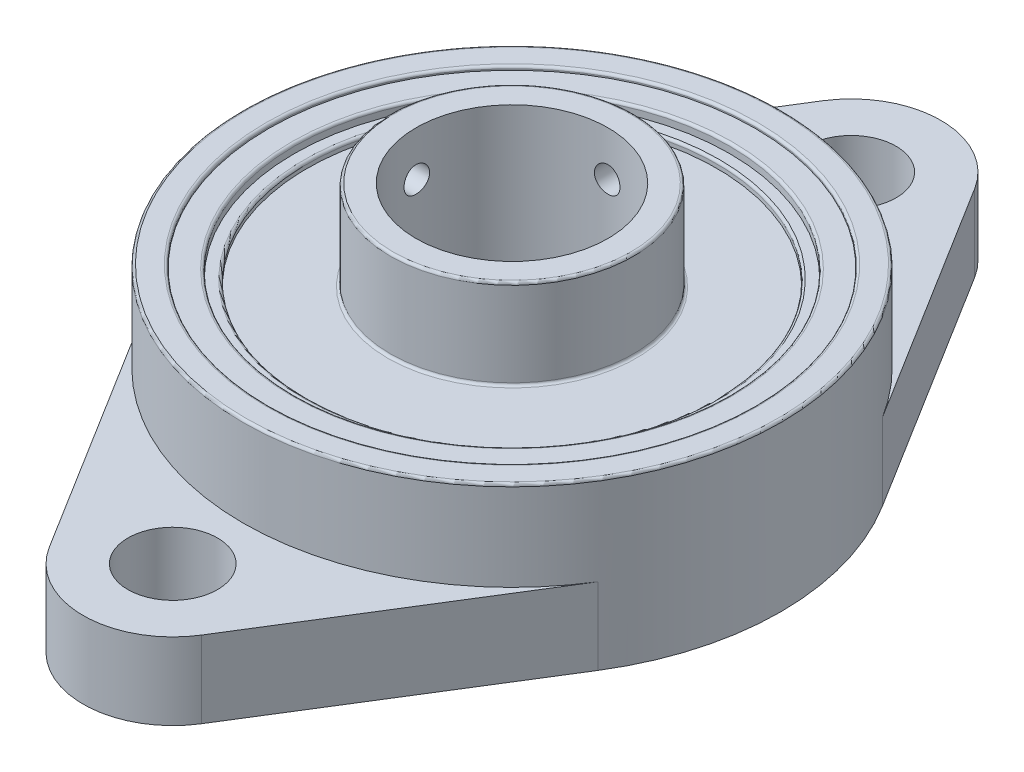
SolidWorks part; units mm, degrees
ref_plane "Front Plane" through (0, 0, 0) normal (0, 0, 1) x (1, 0, 0)
ref_plane "Top Plane" through (0, 0, 0) normal (0, 1, 0) x (1, 0, 0)
ref_plane "Right Plane" through (0, 0, 0) normal (1, 0, 0) x (0, 0, -1)
sketch "Sketch1" plane through (0, 0, 0) normal (0, 1, 0) x (1, 0, 0)
  line L0 (0, -33.5) -> (0, 33.5) construction
  line L1 (0, 0) -> (-50000, 0) construction
  line L2 (17.8302, -11.0943) -> (5.9434, -30.1981)
  line L3 (17.8302, 11.0943) -> (5.9434, 30.1981)
  line L4 (-17.8302, -11.0943) -> (-5.9434, -30.1981)
  line L5 (-17.8302, 11.0943) -> (-5.9434, 30.1981)
  circle A0 centre (0, 0) radius 21
  circle A1 centre (0, 0) radius 7.5
  circle A2 centre (0, 26.5) radius 3.5
  circle A3 centre (0, 0) radius 19
  circle A4 centre (0, 0) radius 9.5
  arc A5 (5.9434, 30.1981) -> (-5.9434, 30.1981) centre (0, 26.5) ccw
  circle A6 centre (0, -26.5) radius 3.5
  arc A7 (-5.9434, -30.1981) -> (5.9434, -30.1981) centre (0, -26.5) ccw
  circle A8 centre (0, 0) radius 17
  circle A9 centre (0, 0) radius 16
  point P6 (0, 0)
  dimension "D1" = 15
  dimension "D2" = 42
  dimension "D5" = 7
  dimension "D3" = 67
  dimension "D4" = 53
  dimension "D6" = 2
  dimension "D7" = 2
  dimension "D8" = 2
  dimension "D9" = 1
extrude "A1" add sketch "Sketch1" along normal blind 6 contours L4 A7 L2 A0 A6 | A0 A3 | L3 A5 L5 A0 A2 region at (11.5292, 0, 20.4237) region at (0, 0, 20.406) region at (-11.5292, 0, -20.4237)
extrude "A" add sketch "Sketch1<3>" along normal blind 13 contours A0 A3 region at (0, 0, 20.406)
sketch "Sketch1<3>" plane through (0, 0, 0) normal (0, 1, 0) x (1, 0, 0) same geometry as "Sketch1"
extrude "A0" add sketch "Sketch1<4>" along normal blind 18.5 contours A4 A1 region at (-9.2313, 0, 0)
sketch "Sketch1<4>" plane through (0, 0, 0) normal (0, 1, 0) x (1, 0, 0) same geometry as "Sketch1"
extrude "Bearing outer d" add sketch "Sketch1<7>" along normal blind 10 from offset 2 separate body contours A8 A9 region at (-16.5192, 0, 0)
sketch "Sketch1<7>" plane through (0, 0, 0) normal (0, 1, 0) x (1, 0, 0) same geometry as "Sketch1"
extrude "Boss-Extrude6" add sketch "Sketch1<8>" along normal blind 11.5 from offset 1.2 contours A3 A8 region at (-18.4626, 0, 0)
sketch "Sketch1<8>" plane through (0, 0, 0) normal (0, 1, 0) x (1, 0, 0) same geometry as "Sketch1"
extrude "Boss-Extrude7" add sketch "Sketch1<9>" along normal blind 10 from offset 1.5 contours A9 A4 region at (-15.5475, 0, 0)
sketch "Sketch1<9>" plane through (0, 0, 0) normal (0, 1, 0) x (1, 0, 0) same geometry as "Sketch1"
sketch "Sketch2" plane through (0, 0, 0) normal (1, 0, 0) x (0, 0, -1)
  line L0 (0, 0) -> (0, 50000) construction
  line L1 (-11.0943, 0) -> (11.0943, 0) construction
  line L2 (9.5, 15) -> (-9.5, 15) construction
  line L3 (9.5, 11.5) -> (9.5, 18.5) construction
  line L4 (-9.5, 18.5) -> (-9.5, 11.5) construction
  circle A0 centre (0, 15) radius 1
  point P4 (0, 0)
  dimension "D1" = 2
extrude "Cut-Extrude1" cut sketch "Sketch2" against normal up to next
sketch "Sketch3" plane through (0, 0, 0) normal (0, 0, 1) x (1, 0, 0)
  line L0 (0, 0) -> (0, 50000) construction
  line L1 (6, 15) -> (-49994, 15) construction
  line L3 (9.5, 11.5) -> (9.5, 18.5) construction
  circle A0 centre (0, 15) radius 1
  point P7 (9.5, 15)
  point P10 (0, 9.9)
  dimension "D1" = 2
extrude "Cut-Extrude2" cut sketch "Sketch3" against normal up to next
fillet "Fillet1" radius 0.2 1 edges at (0, 12, 16)
fillet "Fillet2" radius 0.2 5 edges at (0, 18.5, 9.5) (0, 11.5, 9.5) (0, 13, 21) (0, 13, 19) (0, 12.7, 17)
equation "\"A\"= \"D1@A\""
equation "\"A0\"= \"D1@A0\""
equation "\"A1\"= \"D1@A1\""
equation "\"D1@Bearing outer d\"=\"D1@Boss-Extrude6\" - 1.5"
equation "\"D1@Boss-Extrude6\"=\"D1@A\" - 1.5"
equation "\"D1@Boss-Extrude7\"= \"D1@Bearing outer d\""
equation "\"S\"= \"D19@Boss-Extrude7\""
equation "\"D19@Boss-Extrude6\"=\"D19@Boss-Extrude7\" - 0.3"
equation "\"H\"= \"D3@Sketch1\""
equation "\"J\"= \"D4@Sketch1\""
equation "\"L\"= \"D2@Sketch1\""
equation "\"N\"= \"D5@Sketch1\""
equation "\"d\"= \"D1@Sketch1\""
